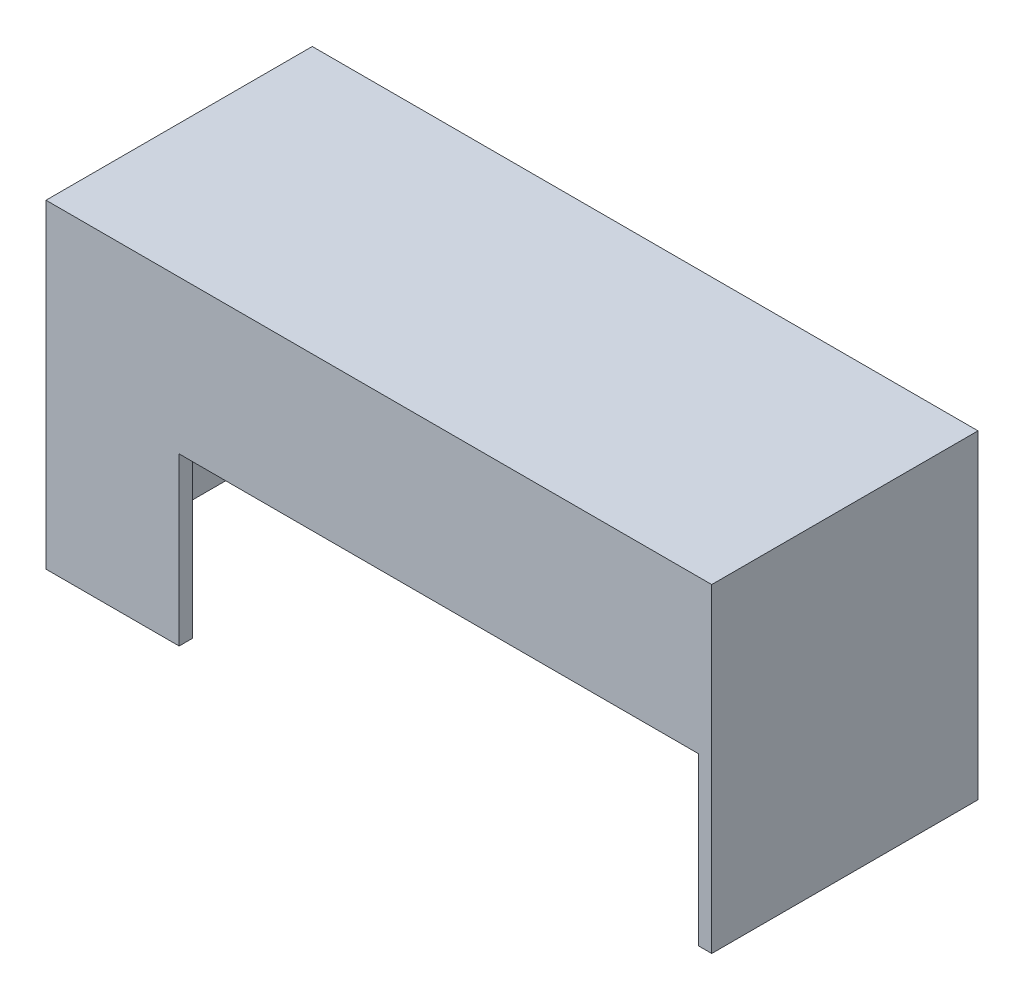
SolidWorks part; units mm, degrees
ref_plane "Front Plane" through (0, 0, 0) normal (0, 0, 1) x (1, 0, 0)
ref_plane "Top Plane" through (0, 0, 0) normal (0, 1, 0) x (1, 0, 0)
ref_plane "Right Plane" through (0, 0, 0) normal (1, 0, 0) x (0, 0, -1)
sketch "Sketch1" plane through (0, 0, 0) normal (0, 0, 1) x (1, 0, 0)
  line L1 (-47.3195, 25.8399) -> (52.6805, 25.8399)
  line L2 (-47.3195, 25.8399) -> (-47.3195, -24.1601)
  line L3 (-47.3195, -24.1601) -> (52.6805, -24.1601)
  line L4 (52.6805, 25.8399) -> (52.6805, -24.1601)
  dimension "D1" = 100
  dimension "D2" = 50
extrude "Boss-Extrude1" add sketch "Sketch1" along normal blind 40
shell "Shell1" thickness 2 removed face at (2.6805, 0.8399, 40)
sketch "Sketch2" plane through (0, -22.1601, 0) normal (0, 1, 0) x (1, 0, 0)
  line L0 (52.6805, -40) -> (-47.3195, -40) construction
  line L1 (-47.3195, 0) -> (52.6805, 0)
  line L2 (-47.3195, 0) -> (-47.3195, -40)
  line L3 (-47.3195, -40) -> (52.6805, -40)
  line L4 (52.6805, 0) -> (52.6805, -40)
  line L5 (52.6805, -40) -> (52.6805, 0) construction
extrude "Cut-Extrude1" cut sketch "Sketch2" against normal blind 40
sketch "Sketch3" plane through (0, 0, 2) normal (0, 0, 1) x (1, 0, 0)
  line L0 (50.6805, -22.1601) -> (50.6805, 23.8399) construction
  line L1 (-45.3195, 23.8399) -> (50.6805, 23.8399)
  line L2 (-45.3195, 23.8399) -> (-45.3195, 2.8399)
  line L3 (-45.3195, 2.8399) -> (50.6805, 2.8399)
  line L4 (50.6805, 23.8399) -> (50.6805, 2.8399)
  line L5 (-45.3195, -22.1601) -> (50.6805, -22.1601) construction
  dimension "D1" = 25
extrude "Boss-Extrude2" add sketch "Sketch3" along normal blind 38
sketch "Sketch4" plane through (0, 0, 40) normal (0, 0, 1) x (1, 0, 0)
  line L0 (-45.3195, -22.1601) -> (50.6805, -22.1601) construction
  line L1 (-47.3195, 25.8399) -> (-27.3195, 25.8399)
  line L2 (-47.3195, 25.8399) -> (-47.3195, -22.1601)
  line L3 (-47.3195, -22.1601) -> (-27.3195, -22.1601)
  line L4 (-27.3195, 25.8399) -> (-27.3195, -22.1601)
  dimension "D1" = 20
extrude "Boss-Extrude3" add sketch "Sketch4" against normal blind 2
shell "Shell2" thickness 2 removed face at (-7.3195, 2.8399, 26.6667)
